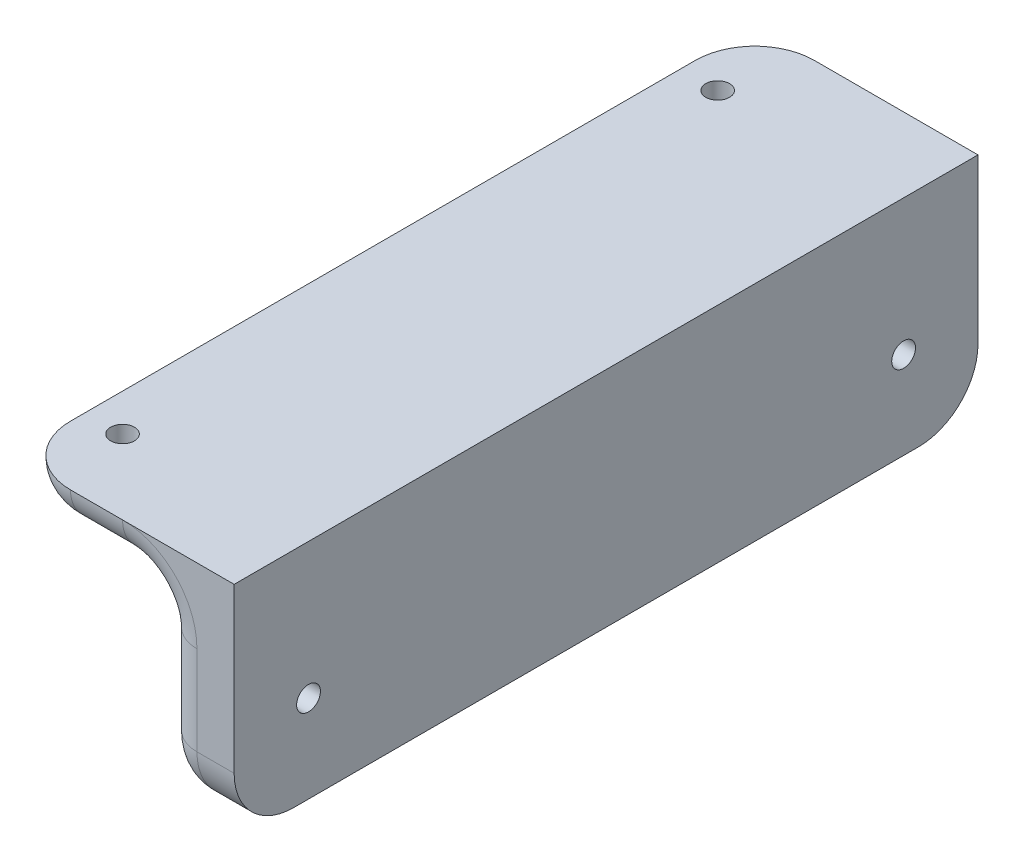
SolidWorks part; units mm, degrees
ref_plane "Alzado" through (0, 0, 0) normal (0, 0, 1) x (1, 0, 0)
ref_plane "Planta" through (0, 0, 0) normal (0, 1, 0) x (1, 0, 0)
ref_plane "Vista lateral" through (0, 0, 0) normal (1, 0, 0) x (0, 0, -1)
sketch "Croquis1" plane through (0, 0, 0) normal (0, 1, 0) x (1, 0, 0)
  line L1 (0, 0) -> (30, 0)
  line L2 (0, 0) -> (0, -100)
  line L3 (0, -100) -> (30, -100)
  line L4 (30, 0) -> (30, -100)
  circle A0 centre (5, -10) radius 1.6
  circle A1 centre (5, -90) radius 1.6
  dimension "D6" = 3.2
  dimension "D7" = 3.2
  dimension "D1" = 30
  dimension "D2" = 100
  dimension "D3" = 80
  dimension "D4" = 10
  dimension "D5" = 25
extrude "Saliente-Extruir1" add sketch "Croquis1" along normal blind 5
sketch "Croquis2" plane through (0, 0, 0) normal (0, -1, 0) x (1, 0, 0)
  line L0 (0, 100) -> (30, 100) construction
  line L1 (30, 0) -> (20, 0)
  line L2 (30, 0) -> (30, 100)
  line L3 (30, 100) -> (20, 100)
  line L4 (20, 0) -> (20, 100)
  dimension "D1" = 10
extrude "Saliente-Extruir2" add sketch "Croquis2" along normal blind 25
sketch "Croquis3" plane through (20, 0, 0) normal (-1, 0, 0) x (0, 0, 1)
  line L0 (0, -13.25) -> (100, -13.25) construction
  line L1 (0, -25) -> (0, 0) construction
  line L2 (100, -25) -> (100, 0) construction
  line L3 (100, 0) -> (0, 0) construction
  circle A0 centre (10, -13.25) radius 1.6
  circle A1 centre (90, -13.25) radius 1.6
  dimension "D2" = 3.2
  dimension "D3" = 3.2
  dimension "D1" = 13.25
  dimension "D4" = 10
  dimension "D5" = 10
extrude "Cortar-Extruir1" cut sketch "Croquis3" against normal up to surface (10 mm away) up to face at (30, -10, 50)
sketch "Croquis4" plane through (0, 0, 0) normal (0, -1, 0) x (1, 0, 0)
  line L0 (20, 0) -> (0, 0) construction
  line L1 (3.3257, 7.1) -> (6.6743, 7.1)
  line L2 (6.6743, 7.1) -> (8.3486, 10)
  line L3 (8.3486, 10) -> (6.6743, 12.9)
  line L4 (6.6743, 12.9) -> (3.3257, 12.9)
  line L5 (3.3257, 12.9) -> (1.6514, 10)
  line L6 (1.6514, 10) -> (3.3257, 7.1)
  line L7 (3.3257, 87.1) -> (6.6743, 87.1)
  line L8 (6.6743, 87.1) -> (8.3486, 90)
  line L9 (8.3486, 90) -> (6.6743, 92.9)
  line L10 (6.6743, 92.9) -> (3.3257, 92.9)
  line L11 (3.3257, 92.9) -> (1.6514, 90)
  line L12 (1.6514, 90) -> (3.3257, 87.1)
  line L13 (0, 100) -> (20, 100) construction
  circle A0 centre (5, 10) radius 2.9 construction
  circle A1 centre (5, 90) radius 2.9 construction
  dimension "D1" = 5.8
  dimension "D2" = 5.8
extrude "Cortar-Extruir2" cut sketch "Croquis4" against normal blind 1
fillet "Redondeo1" radius 8 4 edges at (0, 2.5, 100) (25, -25, 100) (0, 2.5, 0) (25, -25, 0)
sketch "Croquis5" plane through (20, 0, 0) normal (-1, 0, 0) x (0, 0, 1)
  line L0 (100, 0) -> (0, 0) construction
  line L1 (20, 0) -> (80, 0)
  line L2 (20, 0) -> (20, -15)
  line L3 (20, -15) -> (80, -15)
  line L4 (80, 0) -> (80, -15)
  circle A0 centre (10, -13.25) radius 1.6 construction
  dimension "D1" = 60
  dimension "D2" = 10
  dimension "D3" = 15
extrude "Saliente-Extruir3" add sketch "Croquis5" along normal up to surface (20 mm away) up to face at (0, 2.5, 50)
fillet "Redondeo2" radius 5 22 edges at (20, -15, 50) (20, 0, 90) (20, 0, 10) (0, -15, 50) (20, -7.5, 80) (10, -15, 80) (10, 0, 80) (0, 0, 14) (0, 0, 86) (20, -7.5, 20) (10, 0, 20) (0, -7.5, 20) (2.3431, 0, 2.3431) (14, 0, 0) (20, -8.5, 0) (20, -22.6569, 2.3431) (20, -25, 50) (20, -22.6569, 97.6569) (20, -8.5, 100) (0, -7.5, 80) (14, 0, 100) (2.3431, 0, 97.6569)
sketch "Croquis6" plane through (20, 0, 0) normal (-1, 0, 0) x (0, 0, 1)
  circle A0 centre (10, -13.25) radius 2.8
  circle A1 centre (90, -13.25) radius 2.8
  dimension "D1" = 5.6
  dimension "D2" = 5.6
extrude "Cortar-Extruir3" cut sketch "Croquis6" against normal blind 1.5
